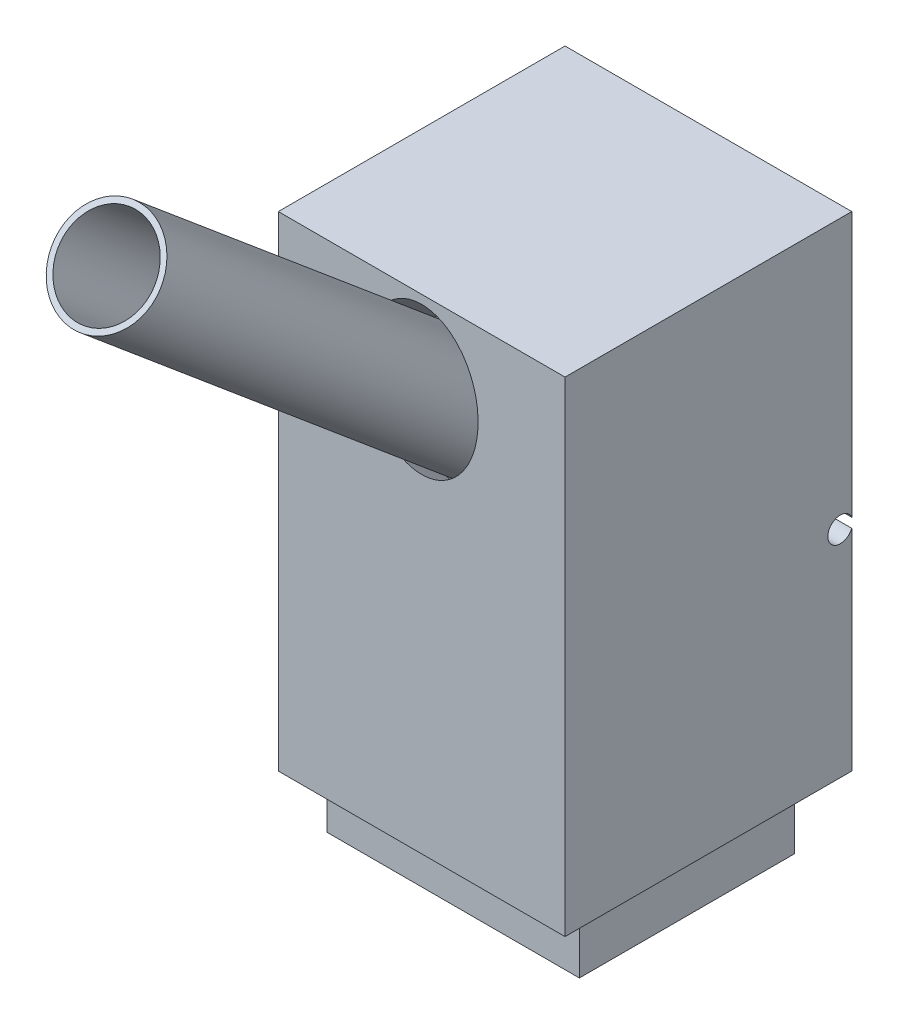
SolidWorks part; units mm, degrees
ref_plane "Front Plane" through (0, 0, 0) normal (0, 0, 1) x (1, 0, 0)
ref_plane "Top Plane" through (0, 0, 0) normal (0, 1, 0) x (1, 0, 0)
ref_plane "Right Plane" through (0, 0, 0) normal (1, 0, 0) x (0, 0, -1)
sketch "Sketch1" plane through (0, 0, 0) normal (0, 0, 1) x (1, 0, 0)
  line L1 (6071.3742, -5703.2258) -> (6096.7742, -5703.2258)
  line L2 (6071.3742, -5703.2258) -> (6071.3742, -5746.1518)
  line L3 (6071.3742, -5746.1518) -> (6096.7742, -5746.1518)
  line L4 (6096.7742, -5703.2258) -> (6096.7742, -5746.1518)
  dimension "D1" = 42.926
  dimension "D2" = 25.4
extrude "Boss-Extrude1" add sketch "Sketch1" along normal blind 25.4 from offset 7.5
sketch "Sketch2" plane through (0, 0, 7.5) normal (0, 0, -1) x (-1, 0, 0)
  line L0 (-6089.9162, -5707.7978) -> (-6096.7742, -5707.7978) construction
  line L1 (-6089.9162, -5707.7978) -> (-6078.2322, -5707.7978)
  line L2 (-6089.9162, -5707.7978) -> (-6089.9162, -5736.7538)
  line L3 (-6089.9162, -5736.7538) -> (-6078.2322, -5736.7538)
  line L4 (-6078.2322, -5707.7978) -> (-6078.2322, -5736.7538)
  line L5 (-6096.7742, -5746.1518) -> (-6096.7742, -5703.2258) construction
  line L6 (-6089.9162, -5707.7978) -> (-6089.9162, -5703.2258) construction
  line L7 (-6096.7742, -5703.2258) -> (-6071.3742, -5703.2258) construction
  line L8 (-6078.2322, -5707.7978) -> (-6071.3742, -5707.7978) construction
  line L9 (-6071.3742, -5703.2258) -> (-6071.3742, -5746.1518) construction
  dimension "D1" = 6.858
  dimension "D2" = 6.858
  dimension "D3" = 4.572
  dimension "D4" = 28.956
extrude "Cut-Extrude1" cut sketch "Sketch2" against normal blind 21.59
ref_plane "Plane3" through (0, -2340.2354, -2788.984) normal (0, -0.6428, -0.766) x (-1, 0, 0)
sketch "Sketch5" plane through (0, -2340.2354, -2788.984) normal (0, -0.6428, -0.766) x (-1, 0, 0)
  line L0 (-6084.0742, -4395.6601) -> (-6096.7742, -4395.6601) construction
  line L2 (-6084.0742, -4395.6601) -> (-6071.3742, -4395.6601) construction
  line L4 (-6071.3742, -4390.0721) -> (-6071.3742, -4422.9554) construction
  line L5 (-6096.7742, -4422.9554) -> (-6096.7742, -4390.0721) construction
  line L6 (-6084.0742, -4395.6601) -> (-6084.0742, -4390.0721) construction
  line L9 (-6096.7742, -4390.0721) -> (-6071.3742, -4390.0721) construction
  circle A0 centre (-6084.0742, -4395.6601) radius 5
  dimension "D1" = 10
  dimension "D2" = 5.588
extrude "Cut-Extrude2" cut sketch "Sketch5" along normal blind 23
sketch "Sketch10" plane through (0, -2340.2354, -2788.984) normal (0, -0.6428, -0.766) x (-1, 0, 0)
  line L0 (-6084.0742, -4395.6601) -> (-6096.7742, -4395.6601) construction
  line L2 (-6084.0742, -4395.6601) -> (-6071.3742, -4395.6601) construction
  circle A0 centre (-6084.0742, -4395.6601) radius 4.5
  circle A3 centre (-6084.0742, -4395.6601) radius 5 construction
  dimension "D1" = 9
extrude "Boss-Extrude2" add sketch "Sketch10" against normal blind 31.75 and the other way blind 21.59 separate body
sketch "Sketch11" plane through (0, -2354.1132, -2805.5229) normal (0, -0.6428, -0.766) x (1, 0, 0)
  line L0 (6084.0742, 4391.1601) -> (6084.0742, 4395.6601) construction
  line L1 (6088.5742, 4395.6601) -> (6071.072, 4395.6601) construction
  circle A0 centre (6084.0742, 4395.6601) radius 4.5 construction
  circle A1 centre (6084.0742, 4395.6601) radius 4
  dimension "D1" = 8
extrude "Cut-Extrude6" cut sketch "Sketch11" against normal through all
hole_wizard "CSK for M3 Flat Head Machine Screw1" positions "Sketch13" profile "Sketch14" countersink size "M3" standard "ANSI Metric"
sketch "Sketch13" plane through (0, 0, 7.5) normal (0, 0, -1) x (-1, 0, 0)
  line L8 (-6075.1842, -5707.0358) -> (-6075.1842, -5703.2258) construction
  line L9 (-6096.7742, -5703.2258) -> (-6071.3742, -5703.2258) construction
  line L11 (-6075.1842, -5707.0358) -> (-6071.3742, -5707.0358) construction
  line L12 (-6071.3742, -5703.2258) -> (-6071.3742, -5746.1518) construction
  line L14 (-6096.7742, -5707.0358) -> (-6092.9642, -5707.0358) construction
  line L15 (-6096.7742, -5746.1518) -> (-6096.7742, -5703.2258) construction
  line L16 (-6092.9642, -5707.0358) -> (-6092.9642, -5703.2258) construction
  line L18 (-6096.7742, -5742.3418) -> (-6092.9642, -5742.3418) construction
  line L19 (-6092.9642, -5742.3418) -> (-6092.9642, -5746.1518) construction
  line L20 (-6071.3742, -5746.1518) -> (-6096.7742, -5746.1518) construction
  line L22 (-6075.1842, -5742.3418) -> (-6075.1842, -5746.1518) construction
  line L24 (-6075.1842, -5742.3418) -> (-6071.3742, -5742.3418) construction
  point P0 (-6092.9642, -5707.0358)
  point P2 (-6075.1842, -5707.0358)
  point P4 (-6075.1842, -5742.3418)
  point P6 (-6092.9642, -5742.3418)
  point P13 (-6092.9642, -5707.0358)
  dimension "D1" = 3.81
  dimension "D2" = 3.81
sketch "Sketch14" plane through (6092.9642, -5707.0358, 7.5) normal (1, 0, 0) x (0, 1, 0)
  line L0 (0, 0) -> (0, 9.906)
  line L1 (0, 9.906) -> (1.7, 8.8845)
  line L2 (1.7, 8.8845) -> (1.7, 1.45)
  line L3 (1.7, 1.45) -> (3.15, 0)
  line L5 (3.15, 0) -> (0, 0)
  line L6 (-1.7, 1.45) -> (-3.15, 0) construction
  line L10 (0, 9.906) -> (-1.7, 8.8845) construction
  line L11 (0, -6.35) -> (0, 107.95) construction
  dimension "Hole Dia." = 3.4
  dimension "Hole Depth" = 9.906
  dimension "Near C'Sink Dia." = 6.3
  dimension "Near C'Sink Angle" = 90
  dimension "Drill Angle" = 118
sketch "Sketch17" plane through (6096.7742, 0, 0) normal (1, 0, 0) x (0, 0, -1)
  line L0 (-7.5, -5746.1518) -> (-7.5, -5703.2258) construction
  line L1 (-8.516, -5727.1018) -> (-8.516, -5746.1518) construction
  line L2 (-32.9, -5746.1518) -> (-7.5, -5746.1518) construction
  circle A0 centre (-8.516, -5727.1018) radius 1.1
  point P4 (0, 0)
  point P5 (-15.12, -5720.8998)
  dimension "D1" = 1.016
  dimension "D2" = 2.2
  dimension "D3" = 19.05
extrude "Cut-Extrude7" cut sketch "Sketch17" against normal through all
sketch "Sketch19" plane through (0, -5746.1518, 0) normal (0, -1, 0) x (1, 0, 0)
  circle A0 centre (6081.5342, 17.66) radius 0.05
  dimension "D1" = 0.1
extrude "Boss-Extrude3" add sketch "Sketch19" along normal blind 0.1
ref_plane "Plane4" through (6096.7742, -5746.1518, 7.5) normal (0, 1, 0) x (1, 0, 0)
sketch "Sketch29" plane through (0, -5746.1518, 0) normal (0, -1, 0) x (1, 0, 0)
  line L0 (6096.7742, 16.6452) -> (6084.0742, 16.6452) construction
  line L3 (6096.7742, 32.9) -> (6096.7742, 7.5) construction
  circle A0 centre (6084.0742, 16.6452) radius 6
  point P0 (6084.0742, 16.6452)
  point P7 (6081.5342, 17.66)
  point P8 (6081.5342, 17.66)
  point P9 (6084.0026, 20.0256)
  dimension "D1" = 12
  dimension "D2" = 12.7
extrude "Cut-Extrude8" cut sketch "Sketch29" against normal up to surface (9.398 mm away) up to face at (6084.0742, -5736.7538, 18.295)
sketch "Sketch30" plane through (0, -5746.1518, 0) normal (0, -1, 0) x (1, 0, 0)
  line L0 (6096.7742, 10.6032) -> (6095.2502, 10.6032) construction
  line L5 (6096.7742, 32.9) -> (6096.7742, 7.5) construction
  line L6 (6095.2502, 7.5) -> (6095.2502, 11.056) construction
  line L11 (6071.3742, 7.5) -> (6096.7742, 7.5) construction
  line L12 (6095.2502, 11.056) -> (6095.2502, 30.106)
  line L13 (6071.3742, 32.9) -> (6071.3742, 7.5) construction
  line L14 (6095.2502, 30.106) -> (6072.8982, 30.106)
  line L15 (6084.0742, 30.106) -> (6084.0742, 27.058) construction
  line L16 (6072.8982, 30.106) -> (6072.8982, 11.056)
  line L18 (6072.8982, 11.056) -> (6075.9462, 11.056)
  line L20 (6075.9462, 11.056) -> (6075.9462, 27.058)
  line L21 (6075.9462, 27.058) -> (6092.2022, 27.058)
  line L22 (6092.2022, 27.058) -> (6092.2022, 11.056)
  line L23 (6092.2022, 11.056) -> (6095.2502, 11.056)
  line L24 (6072.8982, 11.056) -> (6071.3742, 11.056) construction
  dimension "D1" = 1.524
  dimension "D2" = 3.556
  dimension "D3" = 3.048
  dimension "D4" = 19.05
  dimension "D5" = 3.048
extrude "Boss-Extrude4" add sketch "Sketch30" along normal blind 5.334
sketch "Sketch33" plane through (0, 0, 29.09) normal (0, 0, -1) x (-1, 0, 0)
  line L1 (-6088.2295, -5717.6714) -> (-6074.3209, -5717.6714)
  line L2 (-6088.2295, -5717.6714) -> (-6088.2295, -5726.955)
  line L3 (-6088.2295, -5726.955) -> (-6074.3209, -5726.955)
  line L4 (-6074.3209, -5717.6714) -> (-6074.3209, -5726.955)
  point P4 (-6074.2232, -5716.3018)
  point P5 (0, 0)
  point P6 (-6074.3209, -5728.5328)
sketch "Sketch39" plane through (0, -5746.1518, 0) normal (0, -1, 0) x (1, 0, 0)
  line L3 (6071.3742, 32.9) -> (6096.7742, 32.9) construction
  line L5 (6096.7742, 32.9) -> (6095.5042, 32.9)
  point P12 (6095.2264, 27.82)
